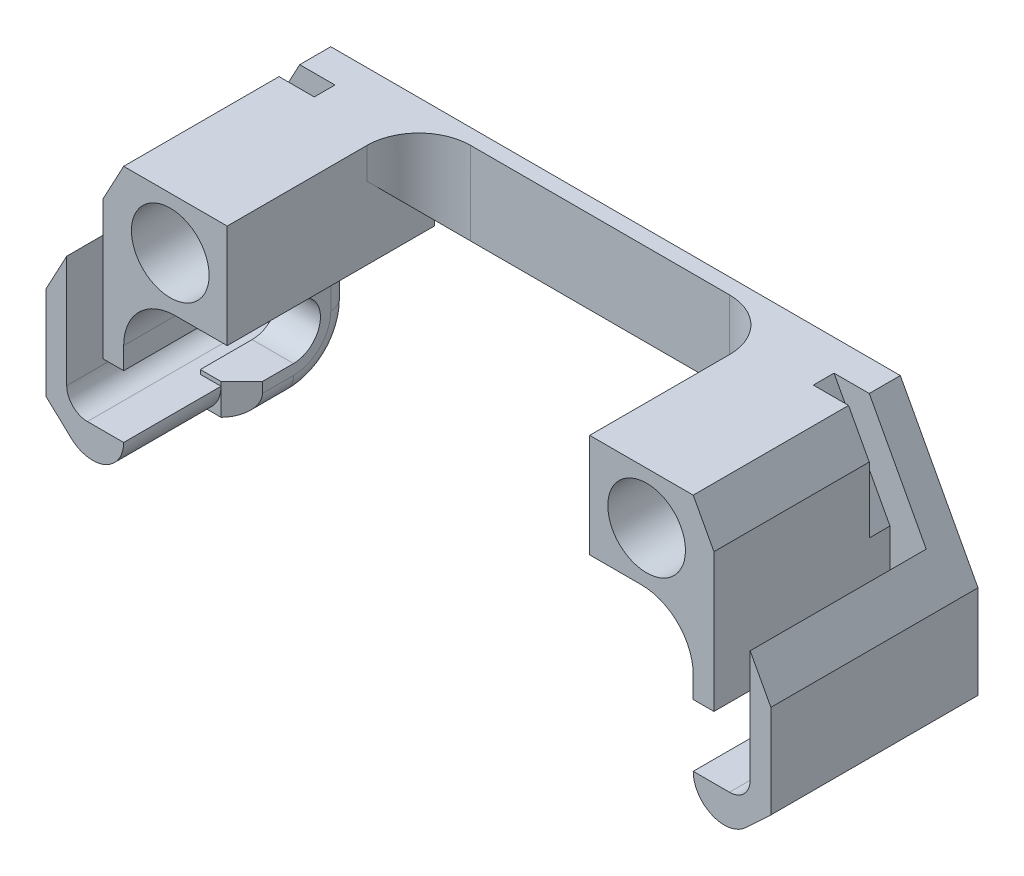
SolidWorks part; units mm, degrees
ref_plane "Front Plane" through (0, 0, 0) normal (0, 0, 1) x (1, 0, 0)
ref_plane "Top Plane" through (0, 0, 0) normal (0, 1, 0) x (1, 0, 0)
ref_plane "Right Plane" through (0, 0, 0) normal (1, 0, 0) x (0, 0, -1)
sketch "Sketch1" plane through (0, 0, 0) normal (0, 0, 1) x (1, 0, 0)
  line L0 (-22.5, 0) -> (22.5, 0)
  line L1 (27.5, -5) -> (27.5, -13.0963)
  line L2 (32.547, -15.2895) -> (35, -13)
  line L3 (35, -13) -> (35, -4)
  line L4 (35, -4) -> (27.5, 10)
  line L5 (27.5, 10) -> (-27.5, 10)
  line L6 (-27.5, 10) -> (-35, -4)
  line L7 (-35, -4) -> (-35, -13)
  line L8 (-35, -13) -> (-32.547, -15.2895)
  line L9 (-27.5, -13.0963) -> (-27.5, -5)
  line L10 (-27.5, 10) -> (-27.5, 0) construction
  line L11 (27.5, 10) -> (27.5, 0) construction
  line L12 (-35, -4) -> (35, -4) construction
  line L13 (0, -4) -> (0, 0) construction
  line L14 (-27.5, -20) -> (27.5, -20) construction
  line L15 (-35, -13) -> (35, -13) construction
  arc A0 (27.5, -13.0963) -> (32.547, -15.2895) centre (30.5, -13.0963) ccw
  arc A1 (-32.547, -15.2895) -> (-27.5, -13.0963) centre (-30.5, -13.0963) ccw
  arc A2 (22.5, 0) -> (27.5, -5) centre (22.5, -5) cw
  arc A3 (-22.5, 0) -> (-27.5, -5) centre (-22.5, -5) ccw
  dimension "D6" = 3
  dimension "D7" = 5
  dimension "D1" = 70
  dimension "D2" = 55
  dimension "D3" = 20
  dimension "D4" = 9
  dimension "D5" = 10
  dimension "D8" = 4
extrude "Boss-Extrude1" add sketch "Sketch1" along normal blind 20
sketch "Sketch3" plane through (0, 0, 0) normal (0, -1, 0) x (1, 0, 0)
  line L0 (-22.5, 20) -> (22.5, 20) construction
  line L1 (-17.5, 20) -> (17.5, 20)
  line L2 (-17.5, 20) -> (-17.5, 1.5)
  line L3 (-17.5, 1.5) -> (17.5, 1.5)
  line L4 (17.5, 20) -> (17.5, 1.5)
  line L5 (0, 1.5) -> (0, 0) construction
  line L6 (-22.5, 0) -> (22.5, 0) construction
  dimension "D1" = 35
  dimension "D2" = 1.5
extrude "Cut-Extrude2" cut sketch "Sketch3" against normal through all
sketch "Sketch2" plane through (0, 0, 20) normal (0, 0, 1) x (1, 0, 0)
  line L1 (-27.5, -13.0963) -> (-30.5295, -13.0963)
  line L2 (-27.5, -13.0963) -> (-27.5, -7.0963)
  line L3 (-27.5, -7.0963) -> (-29.5, -7.0963)
  line L5 (-30.5295, -13.0963) -> (-31, -13.0963)
  line L6 (-29.5, -7.0963) -> (-29.5, 8.5948)
  line L7 (-29.5, 8.5948) -> (-33, 8.5948)
  line L8 (-33, -11.0963) -> (-33, 8.5948)
  arc A0 (-31, -13.0963) -> (-33, -11.0963) centre (-31, -11.0963) cw
  dimension "D4" = 2
  dimension "D1" = 6
  dimension "D2" = 3.5
  dimension "D3" = 2
extrude "Cut-Extrude1" cut sketch "Sketch2" against normal blind 17
mirror "Mirror1" about plane through (0, 0, 0) normal (1, 0, 0) of "Cut-Extrude1"
sketch "Sketch5" plane through (0, 0, 20) normal (0, 0, 1) x (1, 0, 0)
  line L0 (-23, 5) -> (23, 5) construction
  line L1 (0, 5) -> (0, 0) construction
  circle A0 centre (-23, 5) radius 1.75
  circle A1 centre (23, 5) radius 1.75
  dimension "D3" = 3.5
  dimension "D1" = 5
  dimension "D2" = 46
extrude "Cut-Extrude4" cut sketch "Sketch5" against normal through all
sketch "Sketch6" plane through (0, 0, 20) normal (0, 0, 1) x (1, 0, 0)
  circle A2 centre (-23, 5) radius 3.75
  circle A3 centre (-23, 5) radius 3.75
  circle A5 centre (23, 5) radius 3.75
  circle A6 centre (23, 5) radius 3.75
  dimension "D1" = 2
  dimension "D2" = 2
extrude "Cut-Extrude5" cut sketch "Sketch6" against normal blind 7
chamfer "Chamfer1" distance 2 angle 45 1 edges at (0, 0, 1.5)
fillet "Fillet1" radius 5 2 edges at (17.5, 6, 1.5) (-17.5, 6, 1.5)
sketch "Sketch7" plane through (-27.5, 0, 0) normal (1, 0, 0) x (0, 0, -1)
  line L0 (-3, -13.0963) -> (-3, -7.0963) construction
  line L1 (0, -10.0963) -> (0, 0)
  line L2 (-20, 0) -> (0, 0) construction
  line L3 (0, 0) -> (-10.6, 0)
  line L4 (-20, 0) -> (0, 0) construction
  line L5 (-5.6, -7.4963) -> (-5.6, -12.6963) construction
  line L7 (-10.6, 0) -> (-10.6, -7.4963)
  line L9 (-10.6, -7.4963) -> (-5.6, -7.4963)
  line L10 (-5.6, -15.6963) -> (-10.6, -15.6963)
  line L11 (-10.6, -15.6963) -> (-10.6, -12.6963)
  line L13 (-10.6, -12.6963) -> (-5.6, -12.6963)
  line L14 (-10.6, -12.6963) -> (-10.6, -7.4963) construction
  line L16 (-5.6, -12.6963) -> (-5.6, -15.6963) construction
  arc A0 (-5.6, -12.6963) -> (-5.6, -7.4963) centre (-5.6, -10.0963) ccw
  arc A1 (-5.6, -15.6963) -> (0, -10.0963) centre (-5.6, -10.0963) ccw
  circle A2 centre (-5.6, -10.0963) radius 2.6 construction
  circle A3 centre (-5.6, -10.0963) radius 5.6 construction
  point P1 (0, 0)
  point P11 (-11, -0.0986)
  point P13 (-3, -10.0963)
  dimension "D3" = 2.6
  dimension "D2" = 5
  dimension "D1" = 3
extrude "Boss-Extrude5" add sketch "Sketch7" along normal blind 2 and the other way up to vertex (2 mm away) contours L13 A0 L9 L7 L3 L1 A1 L10 L11 other way up to point (-29.5, -7.0963, 20)
mirror "Mirror4" about plane through (0, 0, 0) normal (1, 0, 0) of "Boss-Extrude5"
chamfer "Chamfer2" distance 2 angle 45 4 edges at (25.5, -14.1963, 10.6) (25.5, -4.2482, 10.6) (-25.5, -4.2482, 10.6) (-25.5, -14.1963, 10.6)
fillet "Fillet2" radius 2 6 edges at (25.5, -5.5482, 0) (25.5, -14.0561, 1.6402) (-25.5, -5.5482, 0) (-25.5, -14.0561, 1.6402) (25.5, -15.6963, 7.1) (-25.5, -15.6963, 7.1)
sketch "Sketch8" plane through (-25.5302, 13.6769, 0) normal (-0.8815, 0.4722, 0) x (0, 0, 1)
  line L0 (3, -22.8303) -> (3, -8.4066) construction
  line L1 (5, 2.3556) -> (3, 2.3556)
  line L2 (5, 2.3556) -> (5, -15.1487)
  line L3 (5, -15.1487) -> (3, -15.1487)
  line L4 (3, 2.3556) -> (3, -15.1487)
  line L5 (5, 2.3556) -> (3, -15.1487) construction
  line L6 (5, -15.1487) -> (3, 2.3556) construction
  point P0 (4, -6.3966)
  point P7 (5, -15.1487)
  point P8 (5, 2.3556)
  dimension "D1" = 2
extrude "Cut-Extrude6" cut sketch "Sketch8" against normal blind 3
mirror "Mirror5" about plane through (0, 0, 0) normal (1, 0, 0) of "Cut-Extrude6"
